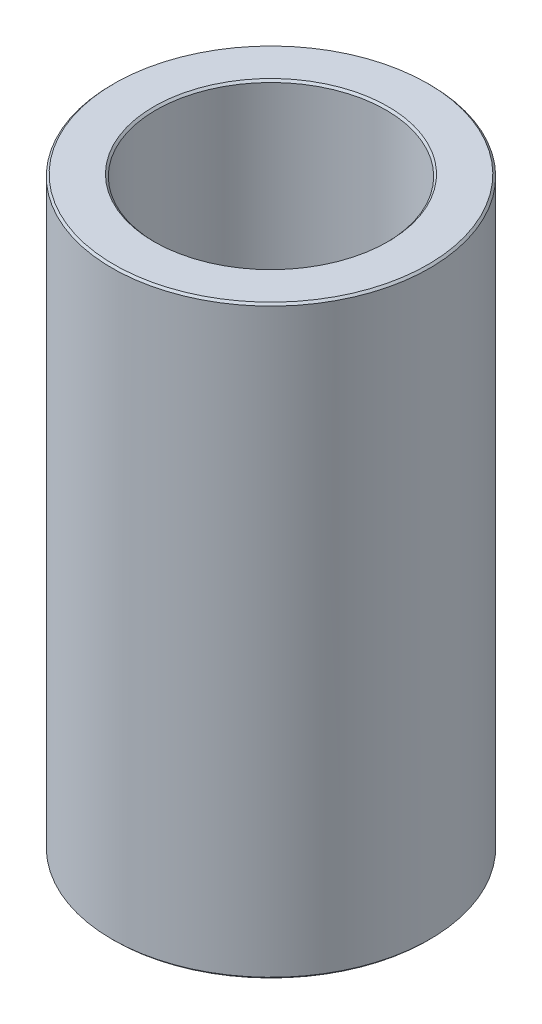
SolidWorks part; units mm, degrees
ref_plane "Front Plane" through (0, 0, 0) normal (0, 0, 1) x (1, 0, 0)
ref_plane "Top Plane" through (0, 0, 0) normal (0, 1, 0) x (1, 0, 0)
ref_plane "Right Plane" through (0, 0, 0) normal (1, 0, 0) x (0, 0, -1)
sketch "Sketch1" plane through (0, 0, 0) normal (0, 1, 0) x (1, 0, 0)
  circle A0 centre (0, 0) radius 57.5
  dimension "SLEEVE_OD" = 115
extrude "Boss-Extrude1" add sketch "Sketch1" along normal blind 211.796
sketch "Sketch2" plane through (0, 0, 0) normal (0, 1, 0) x (1, 0, 0)
  circle A0 centre (0, 0) radius 41.6383
  dimension "BORE_D" = 83.2767
extrude "Cut-Extrude1" cut sketch "Sketch2" along normal through all
chamfer "Chamfer1" distance 0.7282 angle 45 4 edges at (0, 211.796, 41.6383) (0, 0, 41.6383) (0, 0, 57.5) (0, 211.796, 57.5)
